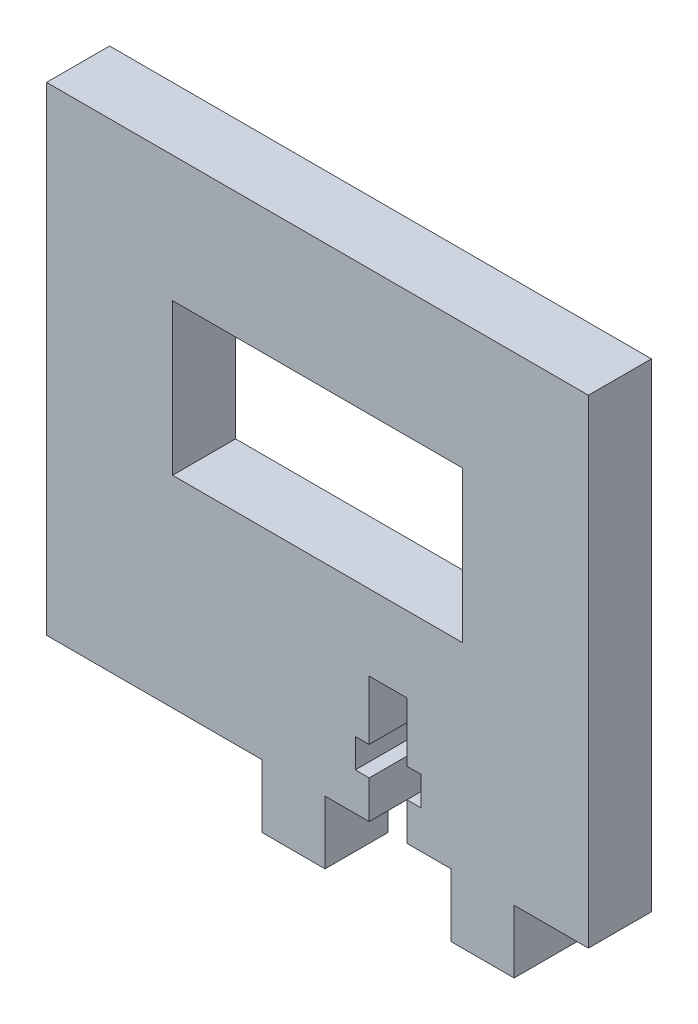
SolidWorks part; units mm, degrees
ref_plane "Front Plane" through (0, 0, 0) normal (0, 0, 1) x (1, 0, 0)
ref_plane "Top Plane" through (0, 0, 0) normal (0, 1, 0) x (1, 0, 0)
ref_plane "Right Plane" through (0, 0, 0) normal (1, 0, 0) x (0, 0, -1)
sketch "Sketch1" plane through (0, 0, 0) normal (0, 0, 1) x (1, 0, 0)
  line L0 (0, 0) -> (-15.8779, 0) construction
  line L1 (-17.1, -6) -> (5.9, -6)
  line L2 (-17.1, -6) -> (-17.1, 6)
  line L3 (-17.1, 6) -> (5.9, 6)
  line L4 (5.9, -6) -> (5.9, 6)
  line L5 (-17.1, -6) -> (5.9, 6) construction
  line L6 (-17.1, 6) -> (5.9, -6) construction
  line L7 (0, 0) -> (0, 16.675) construction
  line L10 (-27.1, -22) -> (-27.1, 16)
  line L11 (-27.1, 16) -> (15.9, 16)
  line L12 (15.9, -22) -> (15.9, 16)
  line L13 (-27.1, -22) -> (15.9, 16) construction
  line L14 (-27.1, 16) -> (15.9, -22) construction
  line L15 (-27.1, -22) -> (15.9, -22)
  circle A0 centre (0, 0) radius 5 construction
  point P0 (-5.6, 0)
  point P9 (-5.6, -3)
  point P15 (0, 0)
  point P16 (0, 0)
  point P17 (0, 0)
  line B0 (-2.6, -19) -> (-2.6, -16.7)
  line B1 (1.5, -16.7) -> (1.5, -12)
  line B2 (-1.5, -12) -> (-1.5, -16.7)
  line B3 (-2.6, -16.7) -> (-1.5, -16.7)
  line B4 (0, -22) -> (0, -10.7792) construction
  line B5 (-1.5, -22) -> (-5, -22)
  line B6 (-5, -27) -> (-10, -27)
  line B7 (-10, -27) -> (-10, -22)
  line B8 (-5, -27) -> (-5, -22)
  line B9 (1.5, -22) -> (5, -22)
  line B10 (5, -22) -> (5, -27)
  line B11 (5, -27) -> (10, -27)
  line B12 (10, -27) -> (10, -22)
  line B13 (-1.5, -22) -> (1.5, -22) construction
  line B14 (1.5, -22) -> (1.5, -19)
  line B15 (1.5, -16.7) -> (2.6, -16.7)
  line B16 (2.6, -19) -> (1.5, -19)
  line B17 (1.5, -12) -> (-1.5, -12)
  line B18 (-1.5, -19) -> (-2.6, -19)
  line B19 (2.6, -16.7) -> (2.6, -19)
  line B20 (-1.5, -19) -> (-1.5, -22)
  line B21 (0, -12) -> (0, -22) construction
  dimension "D1" = 10
  dimension "D2" = 5.9
  dimension "D3" = 17.1
  dimension "D4" = 12
  dimension "D5" = 10
  dimension "D6" = 10
  dimension "D7" = 10
  dimension "D8" = 22
sketch_block_instance "Insert M3 plots ep 5mm-4"
sketch_block "Insert M3 plots ep 5mm" parameters "D1"=10, "D2"=5, "D3"=5
sketch_block_instance "Decoupe Insert M3-4"
sketch_block "Decoupe Insert M3" parameters "D1"=5.2, "D2"=3, "D3"=2.3, "D4"=3, "D5"=10
extrude "Boss-Extrude3" add sketch "Sketch1" along normal blind 5 contours B6 B8 L15 B7 | B11 B12 L15 B10 | B20 B18 B0 B3 B2 B17 B1 B15 B19 B16 B14 L15 L12 L11 L10 L4 L1 L2 L3 region at (-26.5262, -3, 0) region at (-7.5, -24.5, 0) region at (7.5, -24.5, 0)
